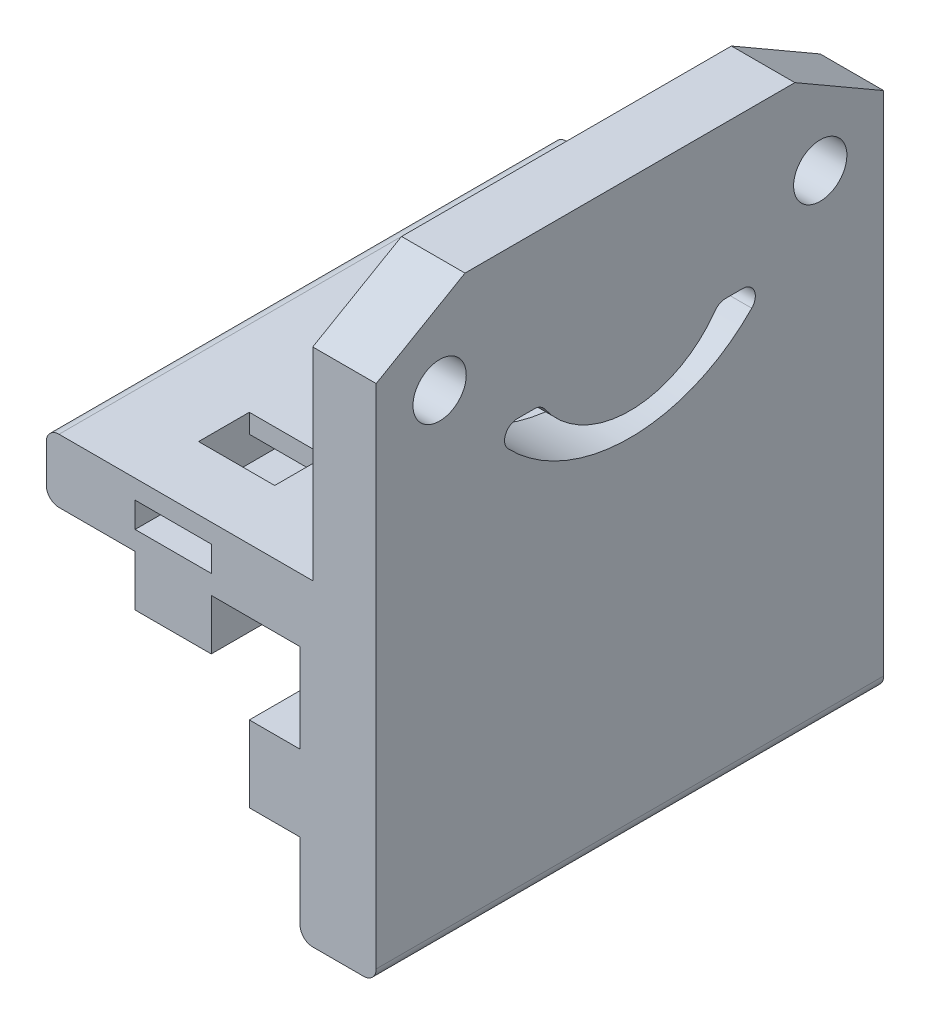
SolidWorks part; units mm, degrees
ref_plane "Plan de face" through (0, 0, 0) normal (0, 0, 1) x (1, 0, 0)
ref_plane "Plan de dessus" through (0, 0, 0) normal (0, 1, 0) x (1, 0, 0)
ref_plane "Plan de droite" through (0, 0, 0) normal (1, 0, 0) x (0, 0, -1)
sketch "Esquisse1" plane through (0, 0, 0) normal (0, 0, 1) x (1, 0, 0)
  line L1 (-13, 25) -> (13, 25)
  line L2 (-13, 25) -> (-13, -25)
  line L3 (-13, -25) -> (13, -25)
  line L4 (13, 25) -> (13, -25)
  dimension "D1" = 26
  dimension "D2" = 50
  dimension "D3" = 13
  dimension "D4" = 25
extrude "Boss.-Extru.1" add sketch "Esquisse1" along normal blind 40
sketch "Esquisse2" plane through (0, 0, 40) normal (0, 0, 1) x (1, 0, 0)
  line L0 (-13, 25) -> (-13, -25) construction
  line L1 (-13, 0) -> (7, 0)
  line L2 (-13, 0) -> (-13, -20)
  line L3 (-13, -20) -> (7, -20)
  line L4 (7, 0) -> (7, -20)
  line L5 (-13, -25) -> (13, -25) construction
  dimension "D1" = 20
  dimension "D2" = 20
  dimension "D3" = 5
extrude "Enlèv. mat.-Extru.1" cut sketch "Esquisse2" against normal through all
sketch "Esquisse3" plane through (0, 0, 40) normal (0, 0, 1) x (1, 0, 0)
  line L0 (7, 0) -> (-13, 0) construction
  line L1 (-6, 0) -> (0, 0)
  line L2 (-6, 0) -> (-6, -4)
  line L3 (-6, -4) -> (0, -4)
  line L4 (0, 0) -> (0, -4)
  line L10 (7, -20) -> (7, 0) construction
  line L11 (7, -7) -> (3, -7)
  line L12 (7, -7) -> (7, -13)
  line L13 (7, -13) -> (3, -13)
  line L14 (3, -7) -> (3, -13)
  line L16 (-13, 25) -> (-13, 0) construction
  dimension "D1" = 4
  dimension "D4" = 7
  dimension "D5" = 6
  dimension "D7" = 6
  dimension "D8" = 4
  dimension "D9" = 7
extrude "Boss.-Extru.2" add sketch "Esquisse3" against normal up to surface (40 mm away) up to face at (-1.5, -5, 0)
sketch "Esquisse7" plane through (0, 0, 40) normal (0, 0, 1) x (1, 0, 0)
  line L0 (13, -25) -> (13, 25) construction
  line L1 (-13, 25) -> (8, 25)
  line L2 (-13, 25) -> (-13, 5)
  line L3 (-13, 5) -> (8, 5)
  line L4 (8, 25) -> (8, 5)
  dimension "D1" = 5
  dimension "D2" = 20
extrude "Enlèv. mat.-Extru.4" cut sketch "Esquisse7" against normal through all
sketch "Esquisse8" plane through (0, 0, 40) normal (0, 0, 1) x (1, 0, 0)
  line L0 (-13, 5) -> (8, 5) construction
  line L1 (-6, 3.5) -> (0, 3.5)
  line L2 (-6, 3.5) -> (-6, 1.5)
  line L3 (-6, 1.5) -> (0, 1.5)
  line L4 (0, 3.5) -> (0, 1.5)
  dimension "D1" = 6
  dimension "D2" = 7
  dimension "D3" = 1.5
  dimension "D4" = 2
extrude "Enlèv. mat.-Extru.5" cut sketch "Esquisse8" against normal through all
sketch "Esquisse9" plane through (0, 5, 0) normal (0, 1, 0) x (1, 0, 0)
  line L0 (-13, 0) -> (8, 0) construction
  line L1 (-6, -31) -> (0, -31)
  line L2 (-6, -31) -> (-6, -35)
  line L3 (-6, -35) -> (0, -35)
  line L4 (0, -31) -> (0, -35)
  line L5 (-6, -5) -> (0, -5)
  line L6 (-6, -5) -> (-6, -9)
  line L7 (-6, -9) -> (0, -9)
  line L8 (0, -5) -> (0, -9)
  line L9 (-13, -40) -> (8, -40) construction
  line L10 (-13, 0) -> (-13, -40) construction
  dimension "D1" = 5
  dimension "D2" = 4
  dimension "D3" = 6
  dimension "D4" = 6
  dimension "D5" = 4
  dimension "D6" = 5
  dimension "D7" = 7
  dimension "D8" = 7
extrude "Enlèv. mat.-Extru.6" cut sketch "Esquisse9" against normal up to surface (3.5 mm away) up to face at (-3, 1.5, 20)
sketch "Esquisse10" plane through (13, 0, 0) normal (1, 0, 0) x (0, 0, -1)
  line L0 (-40, 25) -> (0, 25) construction
  line L1 (-40, -25) -> (-40, 25) construction
  circle A0 centre (-35, 18) radius 2.1
  circle A1 centre (-5, 18) radius 2.1
  dimension "D1" = 4.2
  dimension "D2" = 4.2
  dimension "D3" = 30
  dimension "D4" = 7
  dimension "D5" = 5
  dimension "D6" = 7
extrude "Enlèv. mat.-Extru.7" cut sketch "Esquisse10" against normal through all
chamfer "Chanfrein1" distance 7 angle 30 2 edges at (10.5, 25, 40) (10.5, 25, 0) first distance on face at (10.5, 25, 20)
sketch "Esquisse12" plane through (8, 0, 0) normal (-1, 0, 0) x (0, 0, 1)
  line L0 (9, 13) -> (13, 13)
  line L1 (27, 13) -> (31, 13)
  line L2 (7, 25) -> (33, 25) construction
  line L3 (0, 5) -> (0, 20.9585) construction
  arc A0 (13, 13) -> (27, 13) centre (20, 17.3268) ccw
  arc A1 (9, 13) -> (31, 13) centre (20, 20.6417) ccw
  dimension "D6" = 8.2293
  dimension "D7" = 13.3939
  dimension "D1" = 4
  dimension "D2" = 4
  dimension "D3" = 12
  dimension "D4" = 14
  dimension "D5" = 9
extrude "Enlèv. mat.-Extru.9" cut sketch "Esquisse12" against normal through all
sketch "Esquisse13" plane through (0, 0, 0) normal (0, 0, -1) x (-1, 0, 0)
  line L1 (-13, -25) -> (13, -25)
  line L2 (-13, -25) -> (-13, -20)
  line L3 (-13, -20) -> (13, -20)
  line L4 (13, -25) -> (13, -20)
extrude "Enlèv. mat.-Extru.10" cut sketch "Esquisse13" against normal through all
fillet "Congé1" radius 1 4 edges at (13, -20, 20) (-13, 5, 20) (-13, 0, 20) (7, -20, 20)
fillet "Congé2" radius 1 4 edges at (10.5, 13, 27) (10.5, 13, 13) (10.5, 13, 31) (10.5, 13, 9)
